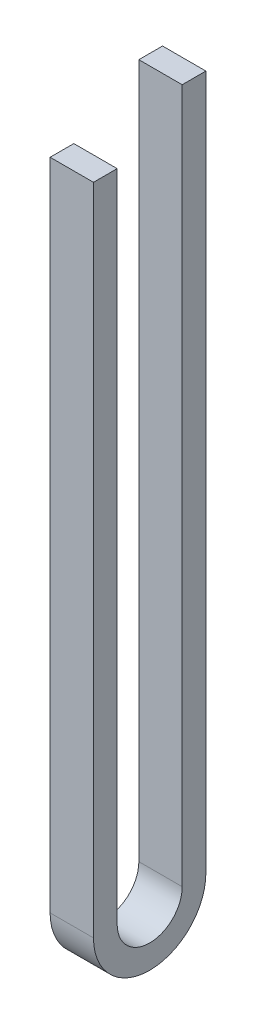
SolidWorks part; units mm, degrees
ref_plane "Front" through (0, 0, 0) normal (0, 0, 1) x (1, 0, 0)
ref_plane "Top" through (0, 0, 0) normal (0, 1, 0) x (1, 0, 0)
ref_plane "Right" through (0, 0, 0) normal (1, 0, 0) x (0, 0, -1)
sketch "Sketch1" plane through (0, 0, 0) normal (1, 0, 0) x (0, 0, -1)
  line L0 (0, 0) -> (0, -414.0425)
  line L1 (71.12, -414.0425) -> (71.12, 25.4)
  line L2 (14.986, 0) -> (14.986, -414.0425)
  line L3 (56.134, -414.0425) -> (56.134, 25.4)
  line L4 (0, 0) -> (14.986, 0)
  line L5 (56.134, 25.4) -> (71.12, 25.4)
  line L7 (0.9525, 25.4) -> (71.4375, 25.4) construction
  arc A0 (0, -414.0425) -> (71.12, -414.0425) centre (35.56, -414.0425) ccw
  arc A1 (14.986, -414.0425) -> (56.134, -414.0425) centre (35.56, -414.0425) ccw
  dimension "D1" = 965.2
  dimension "D2" = 71.12
  dimension "D4" = 41.148
  dimension "D3" = 14.986
extrude "Boss-Extrude1" add sketch "Sketch1" along normal blind 27.432
